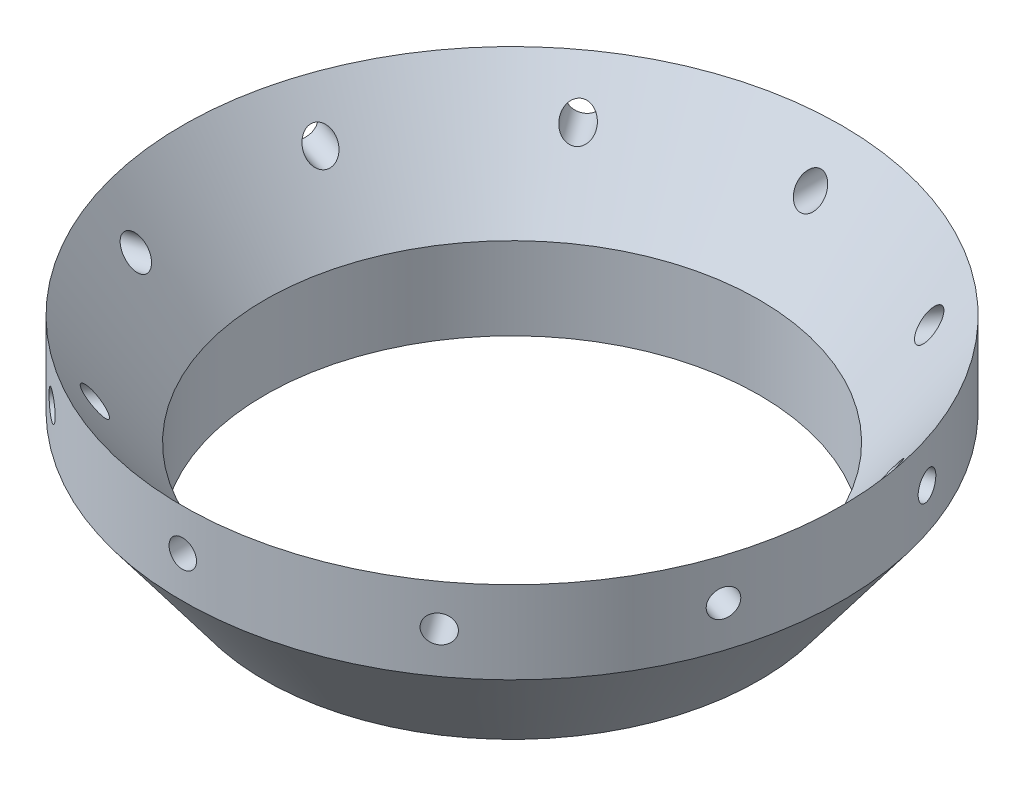
SolidWorks part; units mm, degrees
material "2024-T3"
ref_plane "Front Plane" through (0, 0, 0) normal (0, 0, 1) x (1, 0, 0)
ref_plane "Top Plane" through (0, 0, 0) normal (0, 1, 0) x (1, 0, 0)
ref_plane "Right Plane" through (0, 0, 0) normal (1, 0, 0) x (0, 0, -1)
sketch "Sketch1" plane through (0, 0, 0) normal (0, 0, 1) x (1, 0, 0)
  line L0 (0, 0) -> (0, 220.7687) construction
  line L1 (-57.15, 199.306) -> (-57.15, 218.356)
  line L2 (-57.15, 218.356) -> (-76.2, 243.756)
  line L3 (-76.2, 243.756) -> (-76.2, 224.706)
  line L4 (-76.2, 224.706) -> (-57.15, 199.306)
  dimension "D1" = 57.15
  dimension "D2" = 76.2
  dimension "D3" = 25.4
  dimension "D4" = 19.05
  dimension "D5" = 19.05
revolve "Revolve1" add sketch "Sketch1" angle 360 about L0
sketch "Sketch2" plane through (0, 0, 0) normal (0, 0, 1) x (1, 0, 0)
  line L0 (0, 235.8035) -> (0, 187.481) construction
  line L1 (76.2, 224.706) -> (-76.2, 224.706) construction
  circle A0 centre (0, 234.231) radius 3.175
  dimension "D1" = 9.525
extrude "Cut-Extrude1" cut sketch "Sketch2" against normal through all
ref_axis "Axis1" through (0, 235.8035, 0) along (0, -1, 0)
pattern_circular "CirPattern1" count 10 over 360 about axis through (0, 235.8035, 0) along (0, -1, 0) of "Cut-Extrude1"
